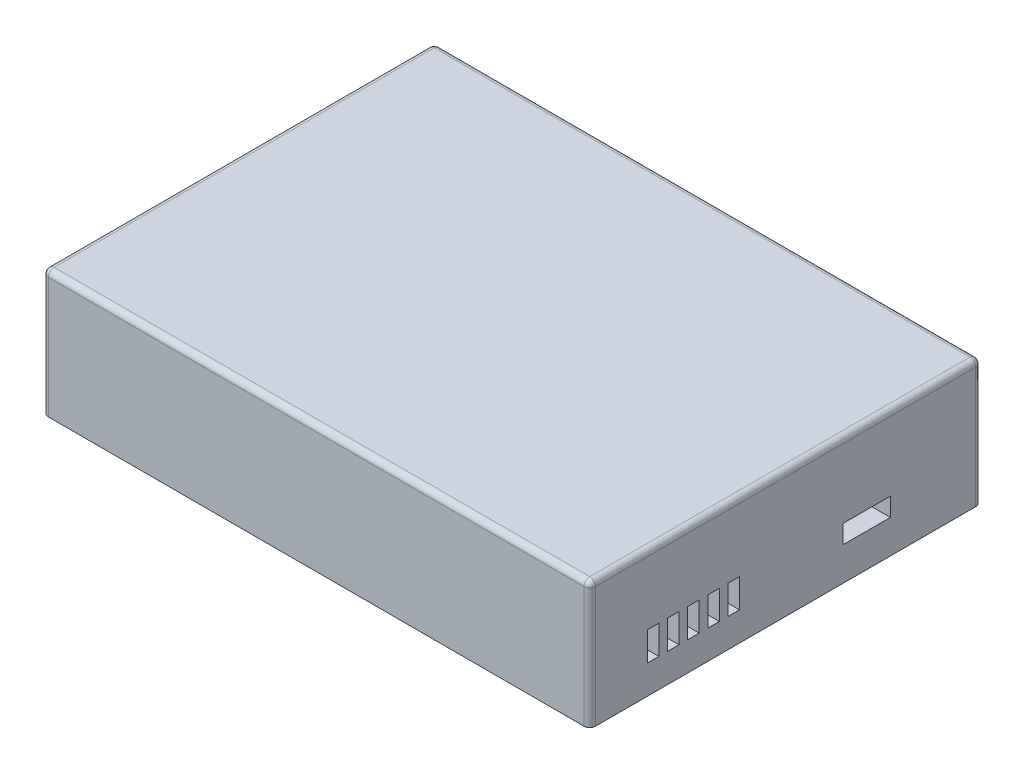
SolidWorks part; units mm, degrees
ref_plane "前视基准面" through (0, 0, 0) normal (0, 0, 1) x (1, 0, 0)
ref_plane "上视基准面" through (0, 0, 0) normal (0, 1, 0) x (1, 0, 0)
ref_plane "右视基准面" through (0, 0, 0) normal (1, 0, 0) x (0, 0, -1)
other "Configuration Table"
sketch "草图1" plane through (0, 0, 0) normal (0, 1, 0) x (1, 0, 0)
  line L6 (47.5, -34) -> (-47.5, -34)
  line L19 (47.5, -34) -> (47.5, 34)
  line L20 (47.5, 34) -> (-47.5, 34)
  line L21 (-47.5, -34) -> (-47.5, 34)
  line L22 (47.5, -34) -> (-47.5, 34) construction
  line L23 (47.5, 34) -> (-47.5, -34) construction
  point P0 (0, 0)
  dimension "D1" = 68
  dimension "D2" = 95
extrude "凸台-拉伸1" add sketch "草图1" along normal blind 2
sketch "草图3" plane through (0, 0, 0) normal (0, -1, 0) x (1, 0, 0)
  line L0 (47.5, -34) -> (-47.5, -34) construction
  line L1 (-47.5, 34) -> (-39.5, 34)
  line L2 (-47.5, 34) -> (-47.5, -34)
  line L3 (-47.5, -34) -> (-39.5, -34)
  line L4 (-39.5, 28) -> (-39.5, -28)
  line L5 (47.5, 34) -> (47.5, -34) construction
  line L6 (-39.5, 34) -> (47.5, 34)
  line L8 (-39.5, 28) -> (47.5, 28)
  line L9 (47.5, 34) -> (47.5, 28)
  line L11 (-39.5, -34) -> (47.5, -34)
  line L13 (-39.5, -28) -> (47.5, -28)
  line L14 (47.5, -34) -> (47.5, -28)
  point P15 (0, 0)
  point P16 (0, 0)
  dimension "D1" = 8
  dimension "D2" = 6
  dimension "D3" = 6
extrude "凸台-拉伸2" add sketch "草图3" along normal blind 2
sketch "草图4" plane through (0, -2, 0) normal (0, -1, 0) x (1, 0, 0)
  line L1 (-47.5, 34) -> (47.5, 34)
  line L2 (-47.5, 34) -> (-47.5, 28)
  line L3 (-45.5, 28) -> (47.5, 28)
  line L4 (47.5, 34) -> (47.5, 28)
  line L6 (-47.5, 28) -> (-47.5, -28)
  line L8 (-45.5, 28) -> (-45.5, -28)
  line L9 (-47.5, -34) -> (47.5, -34)
  line L10 (-47.5, -34) -> (-47.5, -28)
  line L11 (-45.5, -28) -> (47.5, -28)
  line L12 (47.5, -34) -> (47.5, -28)
  point P11 (0, 0)
  point P15 (0, 0)
  point P16 (0, 0)
  dimension "D1" = 2
extrude "凸台-拉伸3" add sketch "草图4" along normal blind 2
sketch "草图5" plane through (0, -4, 0) normal (0, -1, 0) x (1, 0, 0)
  line L0 (-45.5, -28) -> (-45.5, 28) construction
  line L1 (-47.5, 34) -> (-45.5, 34)
  line L2 (-47.5, 34) -> (-47.5, 21)
  line L3 (-47.5, 21) -> (-45.5, 21)
  line L4 (-45.5, 28) -> (-45.5, 21)
  line L10 (-47.5, 34) -> (-47.5, -34) construction
  line L11 (-45.5, 34) -> (47.5, 34)
  line L13 (-45.5, 28) -> (47.5, 28)
  line L14 (47.5, 34) -> (47.5, 28)
  line L19 (-47.5, 8) -> (-45.5, 8)
  line L20 (-47.5, 8) -> (-47.5, -34)
  line L21 (-47.5, -34) -> (-45.5, -34)
  line L22 (-45.5, 8) -> (-45.5, -28)
  line L23 (-47.5, -34) -> (47.5, -34) construction
  line L25 (-45.5, -34) -> (47.5, -34)
  line L27 (-45.5, -28) -> (47.5, -28)
  line L28 (47.5, -34) -> (47.5, -28)
  point P24 (0, 0)
  point P26 (0, 0)
  dimension "D1" = 13
  dimension "D2" = 13
  dimension "D3" = 2
extrude "凸台-拉伸4" add sketch "草图5" along normal blind 2
sketch "草图6" plane through (0, -6, 0) normal (0, -1, 0) x (1, 0, 0)
  line L0 (-47.5, -34) -> (47.5, -34) construction
  line L1 (-47.5, 34) -> (-45.5, 34)
  line L2 (-47.5, 34) -> (-47.5, -34)
  line L3 (-47.5, -34) -> (-45.5, -34)
  line L4 (-45.5, 28) -> (-45.5, -28)
  line L6 (-45.5, 34) -> (47.5, 34)
  line L8 (-45.5, 28) -> (47.5, 28)
  line L9 (47.5, 34) -> (47.5, 28)
  line L10 (-45.5, -34) -> (47.5, -34)
  line L12 (-45.5, -28) -> (47.5, -28)
  line L13 (47.5, -34) -> (47.5, -28)
  point P15 (0, 0)
  point P16 (0, 0)
  dimension "D1" = 2
extrude "凸台-拉伸5" add sketch "草图6" along normal blind 14
sketch "草图7" plane through (-45.5, 0, 0) normal (1, 0, 0) x (0, 0, -1)
  line L0 (-28, -20) -> (-28, 0) construction
  line L1 (-28, -6) -> (-22, -6)
  line L2 (-28, -6) -> (-28, -4)
  line L3 (-28, -4) -> (-22, -4)
  line L4 (-22, -6) -> (-22, -4)
  line L5 (28, -2) -> (-28, -2) construction
  line L7 (-4, -4) -> (2, -4)
  line L8 (-4, -4) -> (-4, -6)
  line L9 (-4, -6) -> (2, -6)
  line L10 (2, -4) -> (2, -6)
  point P12 (0, 0)
  point P13 (0, 0)
  dimension "D1" = 2
  dimension "D2" = 2
  dimension "D3" = 6
  dimension "D4" = 6
  dimension "D5" = 24
extrude "凸台-拉伸6" add sketch "草图7" along normal blind 3
sketch "草图8" plane through (0, -2, 0) normal (0, -1, 0) x (1, 0, 0)
  line L0 (-45.5, -28) -> (-45.5, 28) construction
  line L1 (-45.5, -2) -> (-42.5, -2)
  line L2 (-45.5, -2) -> (-45.5, -4)
  line L3 (-45.5, -4) -> (-42.5, -4)
  line L4 (-42.5, -2) -> (-42.5, -4)
  line L5 (-42.5, -2) -> (-45.5, -2) construction
  point P8 (-42.1405, -4)
  point P10 (0, 0)
  point P11 (-39.5, -4)
  dimension "D1" = 2
  dimension "D2" = 3
extrude "凸台-拉伸7" add sketch "草图8" along normal blind 4
sketch "草图9" plane through (0, -2, 0) normal (0, -1, 0) x (1, 0, 0)
  line L13 (-42.5, 22) -> (-45.5, 22) construction
  line L18 (-42.5, 22) -> (-42.7, 22)
  line L19 (-42.5, 22) -> (-42.5, 23.8)
  line L20 (-42.5, 23.8) -> (-42.7, 23.8)
  line L21 (-42.7, 22) -> (-42.7, 23.8)
  line L23 (-42.7, 24) -> (-42.5, 24)
  line L24 (-42.7, 24) -> (-42.7, 25.8)
  line L25 (-42.7, 25.8) -> (-42.5, 25.8)
  line L26 (-42.5, 24) -> (-42.5, 25.8)
  line L27 (-42.7, 26) -> (-42.5, 26)
  line L28 (-42.7, 26) -> (-42.7, 27.8)
  line L29 (-42.7, 27.8) -> (-42.5, 27.8)
  line L30 (-42.5, 26) -> (-42.5, 27.8)
  line L39 (-42.5, 4) -> (-45.5, 4) construction
  line L40 (-42.7, 4) -> (-42.5, 4)
  line L41 (-42.7, 4) -> (-42.7, 2.2)
  line L42 (-42.7, 2.2) -> (-42.5, 2.2)
  line L43 (-42.5, 4) -> (-42.5, 2.2)
  line L45 (-45.5, -2) -> (-45.5, 28) construction
  line L46 (-42.7, 2) -> (-42.5, 2)
  line L47 (-42.7, 2) -> (-42.7, 0.2)
  line L48 (-42.7, 0.2) -> (-42.5, 0.2)
  line L49 (-42.5, 2) -> (-42.5, 0.2)
  line L50 (-42.7, 0) -> (-42.5, 0)
  line L51 (-42.7, 0) -> (-42.7, -1.8)
  line L52 (-42.7, -1.8) -> (-42.5, -1.8)
  line L53 (-42.5, 0) -> (-42.5, -1.8)
  point P2 (0, 0)
  point P3 (0, 0)
  point P5 (0, 0)
  point P6 (0, 0)
  point P7 (0, 0)
  point P8 (0, 0)
  point P10 (0, 0)
  point P11 (0, 0)
  point P12 (0, 0)
  point P13 (0, 0)
  point P14 (0, 0)
  point P15 (0, 0)
  point P16 (0, 0)
  point P17 (0, 0)
  point P18 (0, 0)
  point P19 (0, 0)
  point P36 (0, 0)
  point P62 (0, 0)
  point P63 (0, 0)
  point P64 (0, 0)
  point P65 (0, 0)
  point P66 (0, 0)
  point P67 (0, 0)
  point P68 (0, 0)
  point P69 (0, 0)
  point P70 (0, 0)
  point P71 (0, 0)
  point P72 (0, 0)
  point P73 (0, 0)
  dimension "D1" = 1.8
  dimension "D2" = 1.8
  dimension "D3" = 1.8
  dimension "D4" = 1.8
  dimension "D5" = 3
  dimension "D6" = 1.8
  dimension "D7" = 1.8
  dimension "D8" = 0.2
  dimension "D9" = 0.2
  dimension "D10" = 0.2
  dimension "D11" = 0.2
  dimension "D12" = 0.2
extrude "凸台-拉伸8" add sketch "草图9" along normal blind 2
sketch "草图13" plane through (0, -20, 0) normal (0, -1, 0) x (1, 0, 0)
  line L0 (47.5, -28) -> (-45.5, -28) construction
  line L1 (-45.5, 28) -> (-42.5, 28)
  line L2 (-45.5, 28) -> (-45.5, -28)
  line L3 (-45.5, -28) -> (-42.5, -28)
  line L4 (-42.5, 28) -> (-42.5, -28)
  dimension "D1" = 3
extrude "凸台-拉伸10" add sketch "草图13" against normal blind 4
chamfer "倒角6" distance 3 angle 45 1 edges at (-42.5, -16, 0)
sketch "草图14" plane through (0, 0, 0) normal (0, -1, 0) x (1, 0, 0)
  line L0 (16.5, 28) -> (16.5, -2)
  line L1 (16.5, 28) -> (19.5, 28)
  line L3 (16.5, -2) -> (19.5, -2)
  line L5 (-39.5, -28) -> (-39.5, 28) construction
  line L6 (19.5, 28) -> (22.5, 28)
  line L8 (19.5, -2) -> (22.5, -2)
  line L9 (22.5, 28) -> (22.5, -2)
  line L10 (-42.5, 28) -> (47.5, 28) construction
  point P9 (0, 0)
  point P10 (0, 0)
  point P11 (0, 0)
  point P12 (0, 0)
  point P13 (0, 0)
  point P14 (0, 0)
  point P15 (0, 0)
  point P16 (0, 0)
  dimension "D1" = 6
  dimension "D2" = 30
  dimension "D3" = 56
  dimension "D4" = 3
  dimension "D5" = 3
extrude "凸台-拉伸11" add sketch "草图14" along normal blind 2
sketch "草图15" plane through (0, 0, 28) normal (0, 0, -1) x (-1, 0, 0)
  line L1 (-19.5, -4) -> (-16.5, -4)
  line L2 (-19.5, -4) -> (-19.5, -6)
  line L3 (-19.5, -6) -> (-16.5, -6)
  line L4 (-16.5, -4) -> (-16.5, -6)
  point P4 (0, 0)
  point P5 (0, 0)
  point P7 (0, 0)
  point P10 (0, 0)
  dimension "D1" = 3
extrude "凸台-拉伸12" add sketch "草图15" along normal blind 3
sketch "草图16" plane through (0, -2, 0) normal (0, -1, 0) x (1, 0, 0)
  line L1 (16.5, 25) -> (18.3, 25)
  line L2 (16.5, 25) -> (16.5, 25.2)
  line L3 (16.5, 25.2) -> (18.3, 25.2)
  line L4 (18.3, 25) -> (18.3, 25.2)
  line L5 (18.5, 25.2) -> (19.5, 25.2)
  line L6 (18.5, 25.2) -> (18.5, 25)
  line L7 (18.5, 25) -> (19.5, 25)
  line L8 (19.5, 25.2) -> (19.5, 25)
  point P10 (0, 0)
  point P11 (18.5, 25.1)
  dimension "D1" = 0.2
  dimension "D2" = 1.8
  dimension "D3" = 0.2
extrude "凸台-拉伸13" add sketch "草图16" along normal blind 2
sketch "草图17" plane through (0, 0, 0) normal (0, -1, 0) x (1, 0, 0)
  line L0 (47.5, -28) -> (-39.5, -28) construction
  line L1 (47.5, 28) -> (39.5, 28)
  line L2 (47.5, 28) -> (47.5, -28)
  line L3 (47.5, -28) -> (39.5, -28)
  line L4 (39.5, 28) -> (39.5, -28)
  dimension "D1" = 8
extrude "凸台-拉伸15" add sketch "草图17" along normal blind 11
sketch "草图18" plane through (0, -11, 0) normal (0, -1, 0) x (1, 0, 0)
  line L0 (47.5, -28) -> (47.5, 28) construction
  line L1 (39.5, 28) -> (47.5, 28)
  line L2 (39.5, 28) -> (39.5, -10)
  line L3 (39.5, -10) -> (47.5, -10)
  line L4 (47.5, 28) -> (47.5, -10)
  line L5 (39.5, 28) -> (39.5, -28) construction
  line L6 (39.5, -18.2) -> (47.5, -18.2)
  line L7 (39.5, -18.2) -> (39.5, -28)
  line L8 (39.5, -28) -> (47.5, -28)
  line L9 (47.5, -18.2) -> (47.5, -28)
  dimension "D1" = 8.2
  dimension "D2" = 38
extrude "凸台-拉伸16" add sketch "草图18" along normal blind 3.2
sketch "草图19" plane through (0, -14.2, 0) normal (0, -1, 0) x (1, 0, 0)
  line L1 (39.5, 28) -> (47.5, 28)
  line L2 (39.5, 28) -> (39.5, -28)
  line L3 (39.5, -28) -> (47.5, -28)
  line L4 (47.5, 28) -> (47.5, -28)
extrude "凸台-拉伸17" add sketch "草图19" along normal blind 5.8
sketch "草图20" plane through (0, -20, 0) normal (0, -1, 0) x (1, 0, 0)
  line L0 (39.5, -28) -> (-42.5, -28) construction
  line L1 (39.5, 28) -> (36.5, 28)
  line L2 (39.5, 28) -> (39.5, -28)
  line L3 (39.5, -28) -> (36.5, -28)
  line L4 (36.5, 28) -> (36.5, -28)
  dimension "D1" = 3
extrude "凸台-拉伸18" add sketch "草图20" against normal blind 4
chamfer "倒角7" distance 3 angle 45 1 edges at (36.5, -16, 0)
chamfer "倒角8" distance 1 angle 45 1 edges at (-47.5, -6, 14.5)
sketch "草图22" plane through (0, -20, 0) normal (0, -1, 0) x (1, 0, 0)
  line L0 (47.5, 34) -> (-47.5, 34) construction
  line L1 (-47.5, 34) -> (-47.5, -34) construction
  line L2 (47.5, -34) -> (47.5, 34) construction
  line L3 (-47.5, -34) -> (47.5, -34) construction
  circle A0 centre (-44.5, 31) radius 2.1
  circle A1 centre (0, 31) radius 2.1
  circle A2 centre (44.5, 31) radius 2.1
  circle A3 centre (44.5, -31) radius 2.1
  circle A4 centre (0, -31) radius 2.1
  circle A5 centre (-44.5, -31) radius 2.1
  point P12 (0, 34)
  point P13 (0, 0)
  point P16 (0, 0)
  point P17 (0, 0)
  point P18 (0, 0)
  point P19 (0, 0)
  point P20 (0, 0)
  point P21 (0, 0)
  point P22 (0, 0)
  dimension "D1" = 2.1
  dimension "D2" = 2.1
  dimension "D3" = 2.1
  dimension "D4" = 2.1
  dimension "D5" = 2.1
  dimension "D6" = 2.1
  dimension "D7" = 3
  dimension "D8" = 3
  dimension "D9" = 3
  dimension "D10" = 3
extrude "切除-拉伸1" cut sketch "草图22" against normal blind 2.6
sketch "草图23" plane through (47.5, 0, 0) normal (1, 0, 0) x (0, 0, -1)
  line L0 (-34, 2) -> (-34, -20) construction
  line L1 (-24, -15) -> (-22, -15)
  line L2 (-24, -15) -> (-24, -10)
  line L3 (-24, -10) -> (-22, -10)
  line L4 (-22, -15) -> (-22, -10)
  line L5 (-34, 2) -> (34, 2) construction
  line L7 (-20.5, -10) -> (-18.5, -10)
  line L8 (-20.5, -10) -> (-20.5, -15)
  line L9 (-20.5, -15) -> (-18.5, -15)
  line L10 (-18.5, -10) -> (-18.5, -15)
  line L11 (-17, -10) -> (-15, -10)
  line L12 (-17, -10) -> (-17, -15)
  line L13 (-17, -15) -> (-15, -15)
  line L14 (-15, -10) -> (-15, -15)
  line L15 (-13.5, -10) -> (-11.5, -10)
  line L16 (-13.5, -10) -> (-13.5, -15)
  line L17 (-13.5, -15) -> (-11.5, -15)
  line L18 (-11.5, -10) -> (-11.5, -15)
  line L19 (-10, -10) -> (-8, -10)
  line L20 (-10, -10) -> (-10, -15)
  line L21 (-10, -15) -> (-8, -15)
  line L22 (-8, -10) -> (-8, -15)
  point P6 (-23, -10)
  dimension "D1" = 10
  dimension "D2" = 2
  dimension "D3" = 5
  dimension "D4" = 12
  dimension "D5" = 1.5
  dimension "D6" = 1.5
  dimension "D7" = 2
  dimension "D8" = 2
  dimension "D9" = 1.5
  dimension "D10" = 1.5
  dimension "D11" = 2
  dimension "D12" = 2
extrude "切除-拉伸2" cut sketch "草图23" against normal through all and the other way through all
fillet "圆角1" radius 1 4 edges at (47.5, -9, -34) (47.5, -9, 34) (-47.5, -9, -34) (-47.5, -9, 34)
fillet "圆角2" radius 1 8 edges at (47.2071, 2, 33.7071) (0, 2, 34) (-47.2071, 2, 33.7071) (-47.5, 2, 0) (-47.2071, 2, -33.7071) (0, 2, -34) (47.2071, 2, -33.7071) (47.5, 2, 0)
